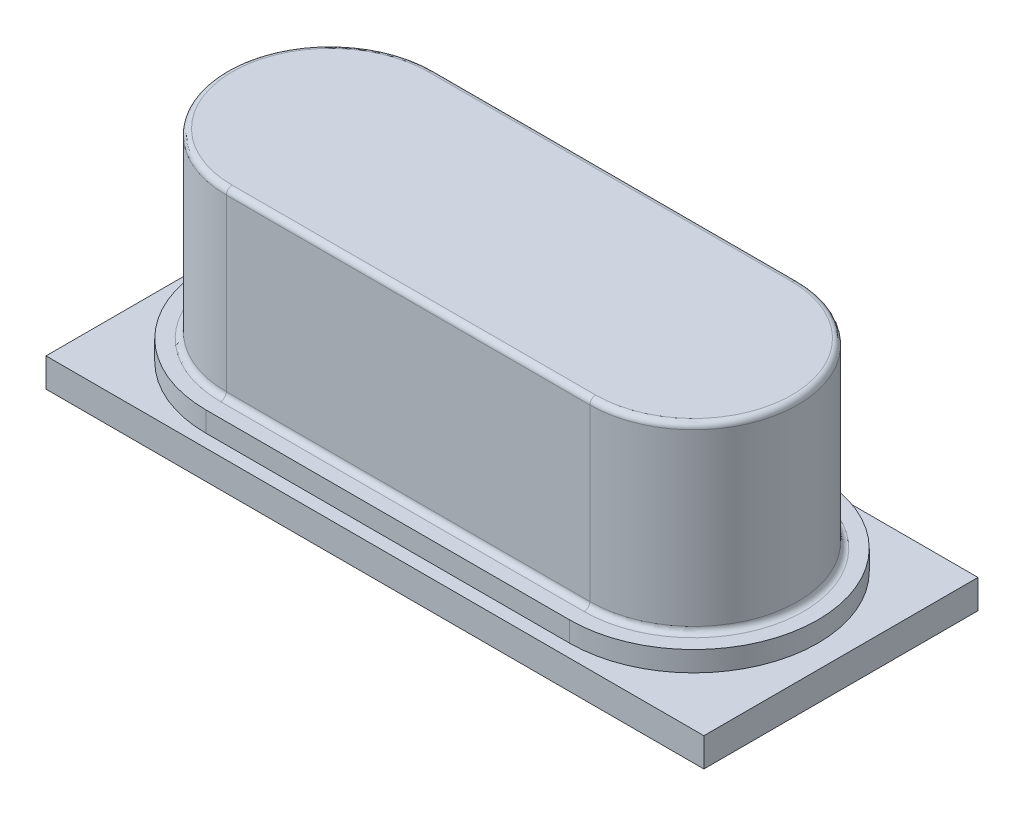
SolidWorks part; units mm, degrees
ref_plane "Front Plane" through (0, 0, 0) normal (0, 0, 1) x (1, 0, 0)
ref_plane "Top Plane" through (0, 0, 0) normal (0, 1, 0) x (1, 0, 0)
ref_plane "Right Plane" through (0, 0, 0) normal (1, 0, 0) x (0, 0, -1)
sketch "Sketch1" plane through (0, 0, 0) normal (0, 1, 0) x (1, 0, 0)
  line L1 (-5.7, -2.375) -> (5.7, -2.375)
  line L2 (-5.7, -2.375) -> (-5.7, 2.375)
  line L3 (-5.7, 2.375) -> (5.7, 2.375)
  line L4 (5.7, -2.375) -> (5.7, 2.375)
  line L5 (-5.7, -2.375) -> (5.7, 2.375) construction
  line L6 (-5.7, 2.375) -> (5.7, -2.375) construction
  point P0 (0, 0)
  dimension "D1" = 4.75
  dimension "D2" = 11.4
extrude "Boss-Extrude1" add sketch "Sketch1" along normal blind 0.5
sketch "Sketch2" plane through (0, 0.5, 0) normal (0, 1, 0) x (1, 0, 0)
  line L0 (-3.15, 0) -> (3.15, 0) construction
  line L1 (-3.15, 1.8) -> (3.15, 1.8)
  line L2 (-3.15, -1.8) -> (3.15, -1.8)
  line L3 (-3.15, 2.15) -> (3.15, 2.15)
  line L4 (-3.15, -2.15) -> (3.15, -2.15)
  arc A0 (-3.15, 1.8) -> (-3.15, -1.8) centre (-3.15, 0) ccw
  arc A1 (3.15, -1.8) -> (3.15, 1.8) centre (3.15, 0) ccw
  arc A2 (3.15, -2.15) -> (3.15, 2.15) centre (3.15, 0) ccw
  arc A3 (-3.15, 2.15) -> (-3.15, -2.15) centre (-3.15, 0) ccw
  point P2 (0, 0)
  dimension "D2" = 6.3
  dimension "D1" = 3.6
  dimension "D3" = 0.35
extrude "Boss-Extrude2" add sketch "Sketch2" along normal blind 3.5 contours L2 A1 L1 A0 region at (0, 0.5, 0)
extrude "Boss-Extrude3" add sketch "Sketch2<3>" along normal blind 0.35
sketch "Sketch2<3>" plane through (0, 0.5, 0) normal (0, 1, 0) x (1, 0, 0) same geometry as "Sketch2"
fillet "Fillet1" radius 0.1 8 edges at (-4.95, 0.85, 0) (0, 0.85, -1.8) (4.95, 0.85, 0) (-4.95, 4, 0) (0, 4, -1.8) (4.95, 4, 0) (0, 4, 1.8) (0, 0.85, 1.8)
